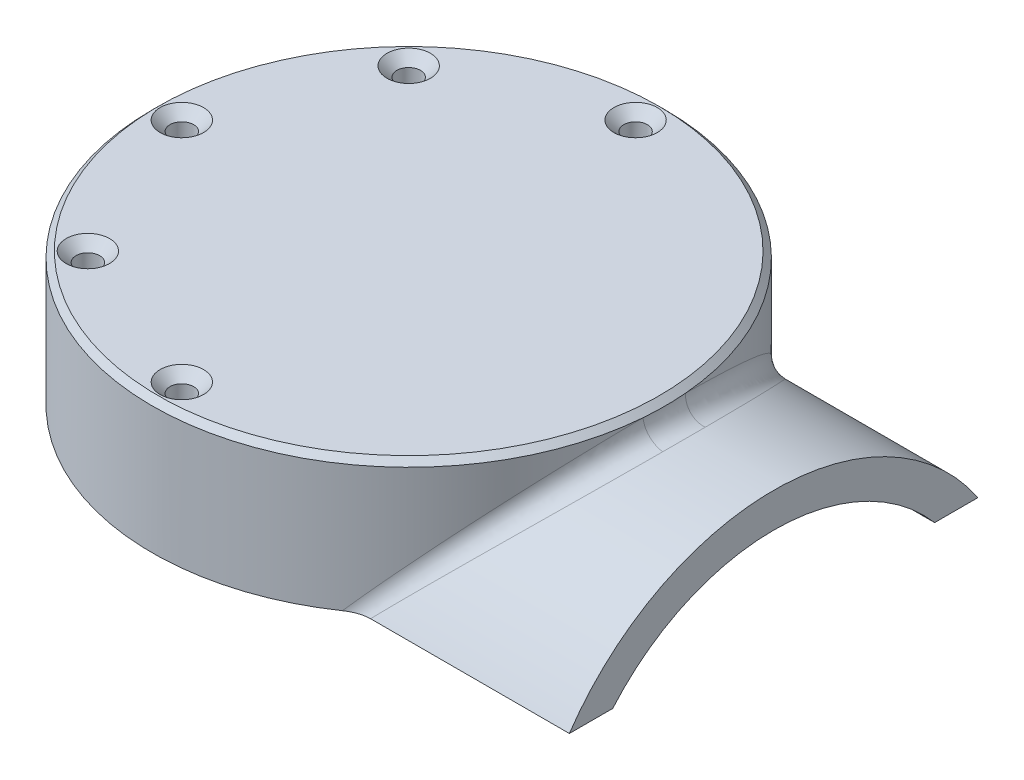
SolidWorks part; units mm, degrees
material "ABS"
ref_plane "Спереди" through (0, 0, 0) normal (0, 0, 1) x (1, 0, 0)
ref_plane "Сверху" through (0, 0, 0) normal (0, 1, 0) x (1, 0, 0)
ref_plane "Справа" through (0, 0, 0) normal (1, 0, 0) x (0, 0, -1)
sketch "Эскиз1" plane through (0, 0, 0) normal (0, 0, 1) x (1, 0, 0)
  line L0 (0, 0) -> (0, 41295.6463) construction
  line L1 (0, 0) -> (-26, 0)
  line L2 (-26, 0) -> (-26, 27.5)
  line L3 (-26, 27.5) -> (0, 27.5)
  line L4 (0, 27.5) -> (0, 0)
  line L5 (0, 0) -> (-50000, 0) construction
  dimension "D1" = 52
  dimension "D2" = 27.5
revolve "Повернуть1" add sketch "Эскиз1" angle 360 about L0
sketch "Эскиз2" plane through (0, 0, 0) normal (0, 0, 1) x (1, 0, 0)
  line L0 (0, 0) -> (50000, 0) construction
  line L1 (-26, 0) -> (26, 0) construction
  line L2 (0, 0) -> (0, 25)
  line L3 (0, 25) -> (37, 25)
  line L4 (37, 25) -> (37, 0)
  line L5 (37, 0) -> (0, 0)
  point P4 (0, 0)
  dimension "D1" = 50
  dimension "D2" = 37
revolve "Повернуть2" add sketch "Эскиз2" angle 360 about L0
chamfer "Фаска1" distance 0.6 angle 45 1 edges at (0, 27.5, -26)
sketch "Эскиз4" plane through (0, 0, 0) normal (0, 0, 1) x (1, 0, 0)
  line L0 (0, 0) -> (0, 50000) construction
  line L1 (0, 0) -> (-25, 0)
  line L2 (-25, 0) -> (-25, 20)
  line L4 (0, 25) -> (0, 0)
  line L6 (0, 25) -> (-21, 25)
  line L7 (-21, 25) -> (-21, 20)
  line L8 (-21, 20) -> (-25, 20)
  line L10 (37, 25) -> (26, 25) construction
  dimension "D1" = 50
  dimension "D2" = 42
  dimension "D3" = 20
revolve "Вырез-Повернуть1" cut sketch "Эскиз4" angle 360 about L0
sketch "Эскиз5" plane through (0, 0, 0) normal (0, 0, 1) x (1, 0, 0)
  line L0 (0, 0) -> (50000, 0) construction
  line L1 (37, 21.5) -> (37, 0)
  line L2 (0, 0) -> (0, 21.5)
  line L3 (0, 21.5) -> (37, 21.5)
  line L4 (37, -25) -> (37, 25) construction
  line L8 (0, 0) -> (37, 0)
  dimension "D1" = 43
revolve "Вырез-Повернуть2" cut sketch "Эскиз5" angle 360 about L0
sketch "Эскиз6" plane through (0, 0, 0) normal (0, 1, 0) x (1, 0, 0)
  line L3 (7.1414, -25) -> (37, -25) construction
  line L4 (7.1414, 25) -> (37, 25)
  line L5 (37, 25) -> (37, -25)
  line L6 (37, -25) -> (7.1414, -25)
  circle A0 centre (0, 0) radius 26 construction
  arc A1 (7.1414, -25) -> (7.1414, 25) centre (0, 0) ccw construction
  arc A2 (7.1414, -25) -> (7.1414, 25) centre (0, 0) cw
extrude "Вырез-Вытянуть1" cut sketch "Эскиз6" against normal through all and the other way blind 14
hole_wizard "Зенковка для винта с потайной головкой M21" positions "Эскиз7" profile "Эскиз8" countersink size "M2" standard "HASCO Metric" end condition through all
sketch "Эскиз7" plane through (0, 27.5, 0) normal (0, 1, 0) x (1, 0, 0)
  line L0 (0, 0) -> (-25.4, 0) construction
  circle A0 centre (0, 0) radius 25.4 construction
  circle A1 centre (0, 0) radius 23 construction
  point P0 (-23, 0)
  dimension "D1" = 46
sketch "Эскиз8" plane through (-23, 27.5, 0) normal (1, 0, 0) x (0, 0, 1)
  line L0 (0, 0) -> (0, 15.8029)
  line L1 (0, 15.8029) -> (1.2, 15.8029)
  line L2 (1.2, 15.8029) -> (1.2, 1)
  line L3 (1.2, 1) -> (2.2, 0)
  line L5 (2.2, 0) -> (0, 0)
  line L6 (-1.2, 1) -> (-2.2, 0) construction
  line L11 (0, -6.35) -> (0, 107.95) construction
  dimension "Диаметр сквозного отверстия" = 2.4
  dimension "Глубина сквозного отверстия" = 15.8029
  dimension "Диаметр передней зенковки" = 4.4
  dimension "Угол передней зенковки" = 90
pattern_circular "Круговой массив1" count 3 every 45 about axis through (0, 27.5, 0) along (0, 1, 0) of "Зенковка для винта с потайной головкой M21" other way count 3
fillet "Скругление1" radius 2 1 edges at (0, 25, -21)
fillet "Скругление2" radius 2 1 edges at (25.9972, 24.9971, -0.3796)
